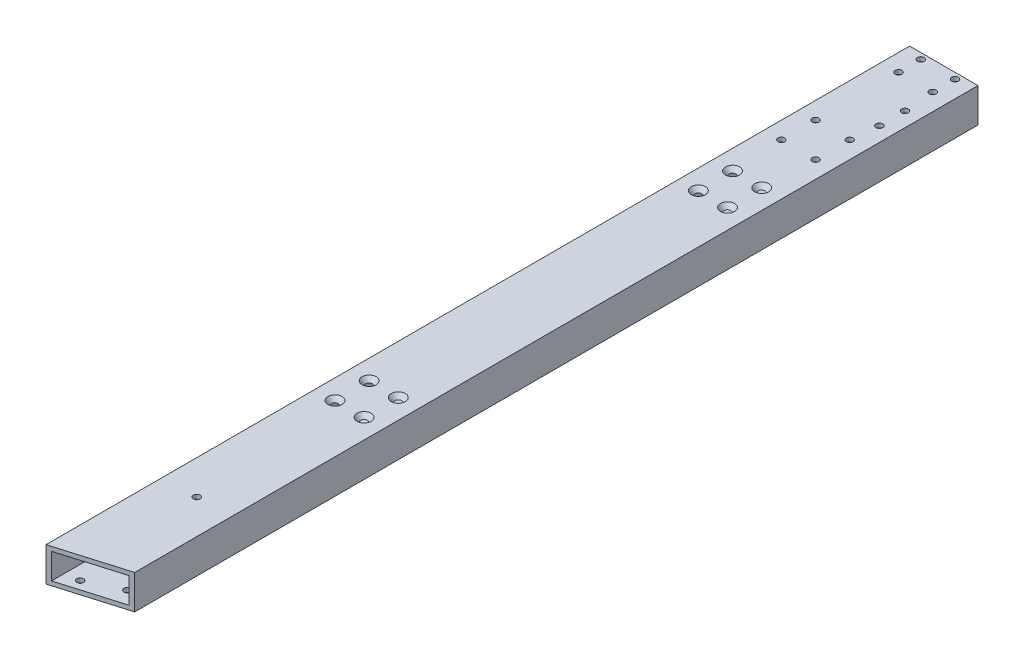
SolidWorks part; units mm, degrees
material "1060 Alloy"
ref_plane "Front Plane" through (0, 0, 0) normal (0, 0, 1) x (1, 0, 0)
ref_plane "Top Plane" through (0, 0, 0) normal (0, 1, 0) x (1, 0, 0)
ref_plane "Right Plane" through (0, 0, 0) normal (1, 0, 0) x (0, 0, -1)
sketch "Sketch1" plane through (0, 0, 0) normal (0, 0, 1) x (1, 0, 0)
  line L0 (-22.225, 9.525) -> (22.225, 9.525)
  line L2 (-25.4, 12.7) -> (25.4, 12.7)
  line L3 (-25.4, 12.7) -> (-25.4, -12.7)
  line L4 (-25.4, -12.7) -> (25.4, -12.7)
  line L5 (25.4, 12.7) -> (25.4, -12.7)
  line L10 (22.225, 9.525) -> (22.225, -9.525)
  line L11 (-22.225, -9.525) -> (22.225, -9.525)
  line L12 (-22.225, 9.525) -> (-22.225, -9.525)
  point P12 (0, 12.7)
  point P14 (25.4, 0)
  dimension "Wall Thickness" = 3.175
  dimension "Outside Width" = 50.8
  dimension "Outside Height" = 25.4
  dimension "Inside Height" = 19.05
  dimension "Inside Width" = 44.45
sketch "Sketch2" plane through (0, 0, 0) normal (1, 0, 0) x (0, 0, -1)
  line L0 (320.675, 0) -> (-320.675, 0)
  point P4 (0, 0)
  point P7 (-320.675, 0)
  point P10 (320.675, 0)
  dimension "Length" = 641.35
sketch "Sketch3" plane through (0, 0, 0) normal (0, 0, 1) x (1, 0, 0)
  line L21 (25.4, 12.7) -> (-25.4, 12.7)
  line L22 (25.4, -12.7) -> (25.4, 12.7)
  line L23 (-25.4, -12.7) -> (25.4, -12.7)
  line L24 (-25.4, 12.7) -> (-25.4, -12.7)
  line L25 (25.4, 12.7) -> (-25.4, 12.7)
  line L26 (25.4, -12.7) -> (25.4, 12.7)
  line L27 (-25.4, -12.7) -> (25.4, -12.7)
  line L28 (-25.4, 12.7) -> (-25.4, -12.7)
  line L29 (22.225, 9.525) -> (-22.225, 9.525)
  line L30 (22.225, -9.525) -> (22.225, 9.525)
  line L31 (-22.225, -9.525) -> (22.225, -9.525)
  line L32 (-22.225, 9.525) -> (-22.225, -9.525)
  line L33 (22.225, 9.525) -> (-22.225, 9.525)
  line L34 (22.225, -9.525) -> (22.225, 9.525)
  line L35 (-22.225, -9.525) -> (22.225, -9.525)
  line L36 (-22.225, 9.525) -> (-22.225, -9.525)
  dimension "D1" = 0
  dimension "D2" = 0
extrude "Boss-Extrude1" add sketch "Sketch3" along normal up to vertex (320.675 mm away) and the other way up to vertex (320.675 mm away) up to point (0, 0, 320.675) other way up to point (0, 0, -320.675)
sketch "Drawing Reference" plane through (0, 0, 0) normal (1, 0, 0) x (0, 0, -1)
  line L0 (-320.675, 0) -> (320.675, 0) construction
  line L1 (0, -12.7) -> (0, 12.7) construction
  line L2 (-320.675, -12.7) -> (320.675, -12.7) construction
  line L5 (-320.675, 12.7) -> (320.675, 12.7) construction
  point P7 (-284.099, 0)
  point P8 (284.099, 0)
  dimension "D1" = 36.576
sketch "Sketch4" plane through (0, 12.7, 0) normal (0, 1, 0) x (1, 0, 0)
  line L0 (-25.4, -320.675) -> (25.4, -305.6274)
  line L1 (25.4, -320.675) -> (25.4, 320.675) construction
  line L2 (25.4, -320.675) -> (-25.4, -320.675)
  dimension "D1" = 16.5
extrude "Cut-Extrude1" cut sketch "Sketch4" against normal through all and the other way through all flip side to cut
sketch "Sketch6" plane through (0, -12.7, 0) normal (0, -1, 0) x (1, 0, 0)
  line L0 (25.4, 305.6274) -> (22.1108, 294.5233) construction
  line L1 (25.4, 279.2824) -> (22.225, 279.2824) construction
  line L2 (25.4, 305.6274) -> (25.4, -320.675) construction
  line L3 (22.225, 279.2824) -> (22.225, 313.1512) construction
  line L4 (22.1108, 294.5233) -> (11.811, 297.5742) construction
  line L5 (-11.811, 250.3501) -> (-11.811, 328.3651) construction
  line L6 (-25.4, 320.675) -> (-27.5213, 313.5136) construction
  line L7 (-25.4, 287.6223) -> (-22.225, 287.6223) construction
  line L8 (-25.4, 320.675) -> (-25.4, -320.675) construction
  line L9 (-22.225, 287.6223) -> (-22.225, 328.3651) construction
  line L10 (-27.5213, 313.5136) -> (-11.811, 308.86) construction
  line L11 (11.811, 250.3501) -> (11.811, 313.1512) construction
  line L12 (-27.5213, 313.5136) -> (-36.5388, 283.071) construction
  line L13 (22.1108, 294.5233) -> (13.0933, 264.0807) construction
  line L14 (-37.6746, 250.3501) -> (48.6057, 250.3501) construction
  line L15 (-11.811, 287.6223) -> (-11.811, 328.3651) construction
  line L16 (11.811, 279.2824) -> (11.811, 313.1512) construction
  line L17 (-36.5388, 283.071) -> (-11.811, 275.7463) construction
  line L18 (13.0933, 264.0807) -> (11.811, 264.4606) construction
  dimension "D1" = 10.414
  dimension "D2" = 10.414
hole_wizard "#10 Clearance Hole1" positions "Sketch7" profile "Sketch8" hole size "#10" standard "ANSI Inch"
sketch "Sketch7" plane through (0, -12.7, 0) normal (0, -1, 0) x (-1, 0, 0)
  point P0 (-11.811, -264.4606)
  point P3 (11.811, -275.7463)
  point P7 (-11.811, -297.5742)
  point P10 (11.811, -308.86)
sketch "Sketch8" plane through (11.811, -12.7, 264.4606) normal (1, 0, 0) x (0, 0, -1)
  line L0 (0, 0) -> (0, 6.5757)
  line L1 (0, 6.5757) -> (2.4892, 5.08)
  line L2 (2.4892, 5.08) -> (2.4892, 0)
  line L5 (2.4892, 0) -> (0, 0)
  line L10 (0, 6.5757) -> (-2.4892, 5.08) construction
  line L11 (0, -6.35) -> (0, 107.95) construction
  dimension "Hole Dia." = 4.9784
  dimension "Hole Depth" = 5.08
  dimension "Drill Angle" = 118
sketch "Sketch9" plane through (0, 12.7, 0) normal (0, 1, 0) x (1, 0, 0)
  line L0 (-12.6238, 316.23) -> (-10.0838, 316.23) construction
  line L2 (-9.1044, 314.5662) -> (-9.0928, 314.5269) construction
  line L3 (10.2362, 316.23) -> (12.7762, 316.23) construction
  line L4 (12.7762, 299.72) -> (10.2362, 299.72) construction
  line L5 (-10.0838, 299.72) -> (-12.6238, 299.72) construction
hole_wizard "#10 Clearance Hole2" positions "Sketch10" profile "Sketch11" hole size "#10" standard "ANSI Inch"
sketch "Sketch10" plane through (0, 12.7, 0) normal (0, 1, 0) x (1, 0, 0)
  point P0 (12.7762, 299.72)
  point P3 (-12.6238, 299.72)
  point P6 (12.7762, 316.23)
  point P9 (-12.6238, 316.23)
sketch "Sketch11" plane through (12.7762, 12.7, -299.72) normal (1, 0, 0) x (0, 0, 1)
  line L0 (0, 0) -> (0, 6.5757)
  line L1 (0, 6.5757) -> (2.4892, 5.08)
  line L2 (2.4892, 5.08) -> (2.4892, 0)
  line L5 (2.4892, 0) -> (0, 0)
  line L10 (0, 6.5757) -> (-2.4892, 5.08) construction
  line L11 (0, -6.35) -> (0, 107.95) construction
  dimension "Hole Dia." = 4.9784
  dimension "Hole Depth" = 5.08
  dimension "Drill Angle" = 118
sketch "Sketch12" plane through (0, 12.7, 0) normal (0, 1, 0) x (1, 0, 0)
  line L0 (-12.7, 238.125) -> (12.7, 238.125) construction
  line L1 (12.7, 238.125) -> (12.7, 212.725) construction
  line L2 (12.7, 212.725) -> (-12.7, 212.725) construction
  line L3 (-12.7, 212.725) -> (-12.7, 238.125) construction
hole_wizard "#10 Clearance Hole3" positions "Sketch13" profile "Sketch14" hole size "#10" standard "ANSI Inch" end condition through all
sketch "Sketch13" plane through (0, 12.7, 0) normal (0, 1, 0) x (1, 0, 0)
  point P0 (-12.7, 212.725)
  point P3 (12.7, 212.725)
  point P6 (12.7, 238.125)
  point P9 (-12.7, 238.125)
  point P12 (14.6226, 277.2519)
  point P15 (14.6226, 258.2019)
sketch "Sketch14" plane through (-12.7, 12.7, -212.725) normal (1, 0, 0) x (0, 0, 1)
  line L0 (0, 0) -> (0, 25.4)
  line L1 (0, 25.4) -> (2.4892, 25.4)
  line L2 (2.4892, 25.4) -> (2.4892, 0)
  line L5 (2.4892, 0) -> (0, 0)
  line L11 (0, -6.35) -> (0, 107.95) construction
  dimension "Thru Hole Dia." = 4.9784
  dimension "Thru Hole Depth" = 25.4
sketch "Sketch17" plane through (0, 12.7, 0) normal (0, 1, 0) x (1, 0, 0)
  point P0 (-0.0762, -234.0972)
hole_wizard "#10 Clearance Hole4" positions "Sketch15" profile "Sketch16" hole size "#10" standard "ANSI Inch" end condition through all
sketch "Sketch15" plane through (0, 12.7, 0) normal (0, 1, 0) x (1, 0, 0)
  point P0 (-0.0762, -234.0972)
sketch "Sketch16" plane through (-0.0762, 12.7, 234.0972) normal (1, 0, 0) x (0, 0, 1)
  line L0 (0, 0) -> (0, 25.4)
  line L1 (0, 25.4) -> (2.4892, 25.4)
  line L2 (2.4892, 25.4) -> (2.4892, 0)
  line L5 (2.4892, 0) -> (0, 0)
  line L11 (0, -6.35) -> (0, 107.95) construction
  dimension "Thru Hole Dia." = 4.9784
  dimension "Thru Hole Depth" = 25.4
hole_wizard "Tap Drill for #10-32 Tap1" positions "Sketch18" profile "Sketch19" hole size "#10-32" standard "ANSI Inch" end condition through all
sketch "Sketch18" plane through (0, -12.7, 0) normal (0, -1, 0) x (-1, 0, 0)
  point P0 (-10.8204, -95.25)
  point P3 (-10.8204, -120.65)
  point P6 (10.8204, -120.65)
  point P9 (10.8204, -95.25)
  point P12 (10.8204, 174.625)
  point P15 (-10.8204, 174.625)
  point P18 (-10.8204, 149.225)
  point P21 (10.8204, 149.225)
sketch "Sketch19" plane through (10.8204, -12.7, 95.25) normal (1, 0, 0) x (0, 0, -1)
  line L0 (0, 0) -> (0, 25.4)
  line L1 (0, 25.4) -> (5.2197, 25.4)
  line L2 (2.0193, 21.7184) -> (2.0193, 0)
  line L5 (2.0193, 0) -> (0, 0)
  line L7 (5.2197, 25.4) -> (2.0193, 21.7184)
  line L8 (-5.2197, 25.4) -> (-2.0193, 21.7184) construction
  line L11 (0, -6.35) -> (0, 107.95) construction
  dimension "Thru Hole Dia." = 4.0386
  dimension "Thru Hole Depth" = 25.4
  dimension "Far C'Sink Dia." = 10.4394
  dimension "Far C'Sink Angle" = 82
equation "\"D1@Drawing Reference\"=\"Outside Width@Sketch1\" * 0.72"
